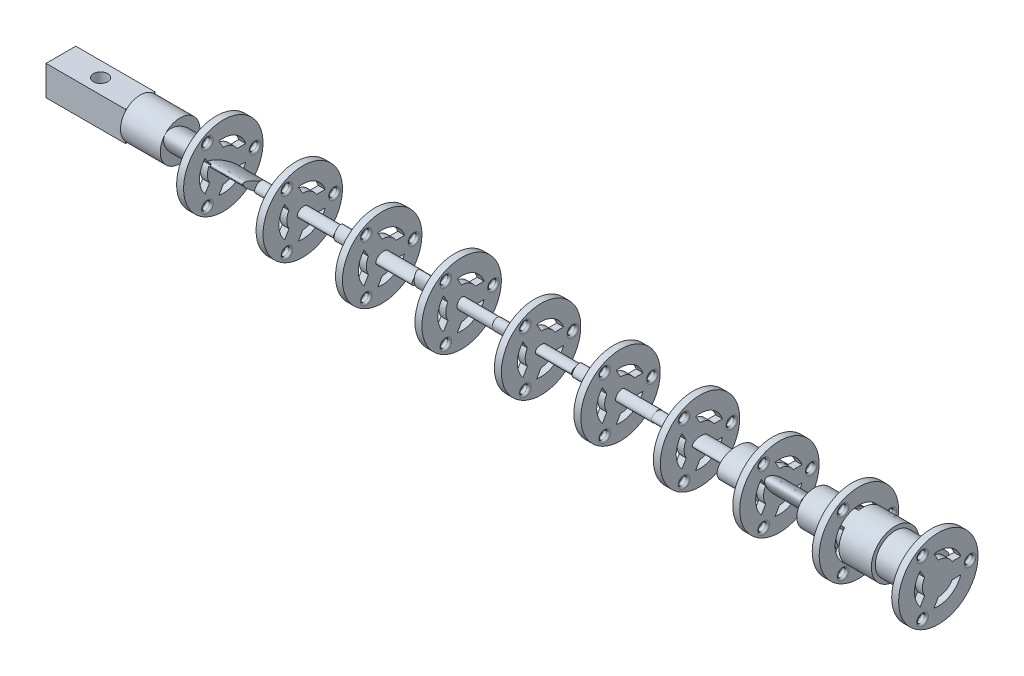
SolidWorks part; units mm, degrees
ref_plane "Front Plane" through (0, 0, 0) normal (0, 0, 1) x (1, 0, 0)
ref_plane "Top Plane" through (0, 0, 0) normal (0, 1, 0) x (1, 0, 0)
ref_plane "Right Plane" through (0, 0, 0) normal (1, 0, 0) x (0, 0, -1)
sketch "Sketch28" plane through (0, 0, 0) normal (1, 0, 0) x (0, 0, -1)
  line L0 (0, 0) -> (0, 30) construction
  line L1 (0, 0) -> (-30, 0) construction
  line L2 (19.0774, 0) -> (-19.0774, 0) construction
  dimension "D1" = 30
sketch "Sketch1" plane through (0, 0, 0) normal (1, 0, 0) x (0, 0, -1)
  line L0 (-3.4986, 3.5721) -> (0, 0) construction
  line L1 (0, 0) -> (-3.565, -3.4916) construction
  line L2 (0, 0) -> (0, 30) construction
  ellipse E0 centre (0, 0) end of major axis (-3.4986, 3.5721) minor radius 4.99
  dimension "ry_1" = 5
  dimension "rz_1" = 4.99
  dimension "phi_1" = 44.404
extrude "Boss-Extrude1" add sketch "Sketch1" along normal blind 10
ref_plane "Plane1" through (10, 0, 0) normal (1, 0, 0) x (0, 0, -1)
sketch "Sketch2" plane through (10, 0, 0) normal (1, 0, 0) x (0, 0, -1)
  line L0 (0, 0) -> (-3.7686, 3.2708) construction
  line L1 (0, 0) -> (-1.737, -2.0014) construction
  line L3 (0, 0) -> (0, 30) construction
  ellipse E0 centre (0, 0) end of major axis (3.7686, -3.2708) minor radius 2.65
  dimension "phi_2" = 49.045
  dimension "ry_2" = 4.99
  dimension "rz_2" = 2.65
extrude "Boss-Extrude2" add sketch "Sketch2" along normal blind 10
ref_plane "Plane2" through (20, 0, 0) normal (1, 0, 0) x (0, 0, -1)
sketch "Sketch3" plane through (20, 0, 0) normal (1, 0, 0) x (0, 0, -1)
  line L0 (0, 0) -> (-4.1746, 2.7518) construction
  line L1 (0, 0) -> (-0.5504, -0.8349) construction
  line L2 (0, 0) -> (0, 30) construction
  ellipse E0 centre (0, 0) end of major axis (-4.1746, 2.7518) minor radius 1
  dimension "ry_3" = 5
  dimension "rz_3" = 1
  dimension "phi_3" = 56.608
extrude "Boss-Extrude3" add sketch "Sketch3" along normal blind 10
ref_plane "Plane3" through (30, 0, 0) normal (1, 0, 0) x (0, 0, -1)
sketch "Sketch4" plane through (30, 0, 0) normal (1, 0, 0) x (0, 0, -1)
  line L0 (-0.6296, 0.7769) -> (0, 0) construction
  line L1 (0, 0) -> (-1.0877, -0.8814) construction
  line L2 (0, 0) -> (0, 30) construction
  ellipse E0 centre (0, 0) end of major axis (-1.0877, -0.8814) minor radius 1
  dimension "ry_4" = 1
  dimension "rz_4" = 1.4
  dimension "phi_4" = 39.018
extrude "Boss-Extrude4" add sketch "Sketch4" along normal blind 10
ref_plane "Plane4" through (40, 0, 0) normal (1, 0, 0) x (0, 0, -1)
sketch "Sketch5" plane through (40, 0, 0) normal (1, 0, 0) x (0, 0, -1)
  line L0 (-0.3391, 0.9407) -> (0, 0) construction
  line L1 (0, 0) -> (-1.3453, -0.485) construction
  line L2 (0, 0) -> (0, 30) construction
  ellipse E0 centre (0, 0) end of major axis (-1.3453, -0.485) minor radius 1
  dimension "ry_5" = 1
  dimension "rz_5" = 1.43
  dimension "phi_5" = 19.824
extrude "Boss-Extrude5" add sketch "Sketch5" along normal blind 10
ref_plane "Plane5" through (50, 0, 0) normal (1, 0, 0) x (0, 0, -1)
sketch "Sketch6" plane through (50, 0, 0) normal (1, 0, 0) x (0, 0, -1)
  line L0 (-0.9649, 0.5281) -> (0, 0) construction
  line L1 (0, 0) -> (-0.8066, -1.4737) construction
  line L2 (0, 0) -> (0, 30) construction
  ellipse E0 centre (0, 0) end of major axis (0.8066, 1.4737) minor radius 1.1
  dimension "ry_6" = 1.1
  dimension "rz_6" = 1.68
  dimension "phi_6" = 61.306
extrude "Boss-Extrude6" add sketch "Sketch6" along normal blind 10
ref_plane "Plane6" through (60, 0, 0) normal (1, 0, 0) x (0, 0, -1)
sketch "Sketch7" plane through (60, 0, 0) normal (1, 0, 0) x (0, 0, -1)
  line L0 (-0.3768, 1.0228) -> (0, 0) construction
  line L1 (0, 0) -> (-1.5764, -0.5808) construction
  line L2 (0, 0) -> (0, 30) construction
  ellipse E0 centre (0, 0) end of major axis (-1.5764, -0.5808) minor radius 1.09
  dimension "ry_7" = 1.09
  dimension "rz_7" = 1.68
  dimension "phi_7" = 20.225
extrude "Boss-Extrude7" add sketch "Sketch7" along normal blind 10
ref_plane "Plane7" through (70, 0, 0) normal (1, 0, 0) x (0, 0, -1)
sketch "Sketch8" plane through (70, 0, 0) normal (1, 0, 0) x (0, 0, -1)
  line L0 (-0.0903, 1.9779) -> (0, 0) construction
  line L1 (0, 0) -> (-1.0689, -0.0488) construction
  line L2 (0, 0) -> (0, 30) construction
  ellipse E0 centre (0, 0) end of major axis (0.0903, -1.9779) minor radius 1.07
  dimension "ry_8" = 1.98
  dimension "rz_8" = 1.07
  dimension "phi_8" = 2.613
extrude "Boss-Extrude8" add sketch "Sketch8" along normal blind 10
ref_plane "Plane8" through (80, 0, 0) normal (1, 0, 0) x (0, 0, -1)
sketch "Sketch9" plane through (80, 0, 0) normal (1, 0, 0) x (0, 0, -1)
  line L0 (-1.0857, 0.3131) -> (0, 0) construction
  line L1 (0, 0) -> (-0.3769, -1.3067) construction
  line L2 (0, 0) -> (0, 30) construction
  ellipse E0 centre (0, 0) end of major axis (-0.3769, -1.3067) minor radius 1.13
  dimension "ry_9" = 1.13
  dimension "rz_9" = 1.36
  dimension "phi_9" = 73.912
extrude "Boss-Extrude9" add sketch "Sketch9" along normal blind 10
ref_plane "Plane9" through (90, 0, 0) normal (1, 0, 0) x (0, 0, -1)
sketch "Sketch10" plane through (90, 0, 0) normal (1, 0, 0) x (0, 0, -1)
  line L0 (-0.6242, 1.5057) -> (0, 0) construction
  line L1 (0, 0) -> (-1.2101, -0.5017) construction
  line L2 (0, 0) -> (0, 30) construction
  ellipse E0 centre (0, 0) end of major axis (-0.6242, 1.5057) minor radius 1.31
  dimension "ry_10" = 1.63
  dimension "rz_10" = 1.31
  dimension "phi_10" = 22.517
extrude "Boss-Extrude10" add sketch "Sketch10" along normal blind 10
ref_plane "Plane10" through (100, 0, 0) normal (1, 0, 0) x (0, 0, -1)
sketch "Sketch11" plane through (100, 0, 0) normal (1, 0, 0) x (0, 0, -1)
  line L0 (-1.4393, 0.0443) -> (0, 0) construction
  line L1 (0, 0) -> (-0.0308, -0.9995) construction
  line L2 (0, 0) -> (0, 30) construction
  ellipse E0 centre (0, 0) end of major axis (-1.4393, 0.0443) minor radius 1
  dimension "ry_11" = 1.44
  dimension "rz_11" = 1
  dimension "phi_11" = 88.236
extrude "Boss-Extrude11" add sketch "Sketch11" along normal blind 10
ref_plane "Plane11" through (110, 0, 0) normal (1, 0, 0) x (0, 0, -1)
sketch "Sketch12" plane through (110, 0, 0) normal (1, 0, 0) x (0, 0, -1)
  line L0 (-0.6772, 0.7358) -> (0, 0) construction
  line L1 (0, 0) -> (-1.111, -1.0226) construction
  line L2 (0, 0) -> (0, 30) construction
  ellipse E0 centre (0, 0) end of major axis (-1.111, -1.0226) minor radius 1
  dimension "ry_12" = 1
  dimension "rz_12" = 1.51
  dimension "phi_12" = 42.628
extrude "Boss-Extrude12" add sketch "Sketch12" along normal blind 10
ref_plane "Plane12" through (120, 0, 0) normal (1, 0, 0) x (0, 0, -1)
sketch "Sketch13" plane through (120, 0, 0) normal (1, 0, 0) x (0, 0, -1)
  line L0 (-0.6241, 0.7813) -> (0, 0) construction
  line L1 (0, 0) -> (-1.0861, -0.8675) construction
  line L2 (0, 0) -> (0, 30) construction
  ellipse E0 centre (0, 0) end of major axis (-1.0861, -0.8675) minor radius 1
  dimension "ry_13" = 1
  dimension "rz_13" = 1.39
  dimension "phi_13" = 38.617
extrude "Boss-Extrude13" add sketch "Sketch13" along normal blind 10
ref_plane "Plane13" through (130, 0, 0) normal (1, 0, 0) x (0, 0, -1)
sketch "Sketch14" plane through (130, 0, 0) normal (1, 0, 0) x (0, 0, -1)
  line L0 (-0.3079, 0.9514) -> (0, 0) construction
  line L1 (0, 0) -> (-1.332, -0.4311) construction
  line L2 (0, 0) -> (0, 30) construction
  ellipse E0 centre (0, 0) end of major axis (1.332, 0.4311) minor radius 1
  dimension "ry_14" = 1
  dimension "rz_14" = 1.4
  dimension "phi_14" = 17.934
extrude "Boss-Extrude14" add sketch "Sketch14" along normal blind 10
ref_plane "Plane14" through (140, 0, 0) normal (1, 0, 0) x (0, 0, -1)
sketch "Sketch15" plane through (140, 0, 0) normal (1, 0, 0) x (0, 0, -1)
  line L0 (-0.095, 0.9955) -> (0, 0) construction
  line L1 (0, 0) -> (-1.9611, -0.1871) construction
  line L2 (0, 0) -> (0, 30) construction
  ellipse E0 centre (0, 0) end of major axis (-1.9611, -0.1871) minor radius 1
  dimension "ry_15" = 1
  dimension "rz_15" = 1.97
  dimension "phi_15" = 5.449
extrude "Boss-Extrude15" add sketch "Sketch15" along normal blind 10
ref_plane "Plane15" through (150, 0, 0) normal (1, 0, 0) x (0, 0, -1)
sketch "Sketch16" plane through (150, 0, 0) normal (1, 0, 0) x (0, 0, -1)
  line L0 (-0.151, 3.3766) -> (0, 0) construction
  line L1 (0, 0) -> (-4.8252, -0.2158) construction
  line L3 (0, 0) -> (0, 30) construction
  ellipse E0 centre (0, 0) end of major axis (-4.8252, -0.2158) minor radius 3.38
  dimension "ry_16" = 3.38
  dimension "rz_16" = 4.83
  dimension "phi_16" = 2.561
extrude "Boss-Extrude16" add sketch "Sketch16" along normal blind 10
ref_plane "Plane16" through (160, 0, 0) normal (1, 0, 0) x (0, 0, -1)
sketch "Sketch17" plane through (160, 0, 0) normal (1, 0, 0) x (0, 0, -1)
  line L0 (-3.5412, 3.5299) -> (0, 0) construction
  line L1 (0, 0) -> (-1.1507, -1.1544) construction
  line L2 (0, 0) -> (0, 30) construction
  ellipse E0 centre (0, 0) end of major axis (-3.5412, 3.5299) minor radius 1.63
  dimension "ry_17" = 5
  dimension "rz_17" = 1.63
  dimension "phi_17" = 45.092
extrude "Boss-Extrude17" add sketch "Sketch17" along normal blind 10
ref_plane "Plane17" through (170, 0, 0) normal (1, 0, 0) x (0, 0, -1)
sketch "Sketch18" plane through (170, 0, 0) normal (1, 0, 0) x (0, 0, -1)
  line L0 (-4.3864, 2.0693) -> (0, 0) construction
  line L1 (0, 0) -> (-1.8816, -3.9885) construction
  line L2 (0, 0) -> (0, 30) construction
  ellipse E0 centre (0, 0) end of major axis (-4.3864, 2.0693) minor radius 4.41
  dimension "ry_18" = 4.85
  dimension "rz_18" = 4.41
  dimension "phi_18" = 64.744
extrude "Boss-Extrude18" add sketch "Sketch18" along normal blind 10
ref_plane "Plane18" through (180, 0, 0) normal (1, 0, 0) x (0, 0, -1)
sketch "Sketch19" plane through (180, 0, 0) normal (1, 0, 0) x (0, 0, -1)
  line L0 (-3.7914, 4.6503) -> (0, 0) construction
  line L1 (0, 0) -> (-4.6503, -3.7914) construction
  line L2 (0, 0) -> (0, 30) construction
  ellipse E0 centre (0, 0) end of major axis (-4.6503, -3.7914) minor radius 6
  dimension "ry_19" = 6
  dimension "rz_19" = 6
  dimension "phi_19" = 39.19
extrude "Boss-Extrude19" add sketch "Sketch19" along normal blind 10
ref_plane "Plane19" through (190, 0, 0) normal (1, 0, 0) x (0, 0, -1)
sketch "Sketch20" plane through (190, 0, 0) normal (1, 0, 0) x (0, 0, -1)
  line L0 (-4.6038, 1.9508) -> (0, 0) construction
  line L1 (0, 0) -> (-1.9508, -4.6038) construction
  line L2 (0, 0) -> (0, 30) construction
  ellipse E0 centre (0, 0) end of major axis (-4.6038, 1.9508) minor radius 5
  dimension "ry_20" = 5
  dimension "rz_20" = 5
  dimension "phi_20" = 67.036
extrude "Boss-Extrude20" add sketch "Sketch20" along normal blind 10
sketch "Sketch21" plane through (0, 0, 0) normal (0, 1, 0) x (1, 0, 0)
  line L0 (0, 0) -> (200, 0) construction
  line L1 (19.125, 0) -> (20.875, 0)
  line L2 (19.125, 0) -> (19.125, -10)
  line L3 (19.125, -10) -> (20.875, -10)
  line L4 (20.875, 0) -> (20.875, -10)
  line L5 (200, -5) -> (200, 5) construction
  point P6 (20, -10)
  dimension "D1" = 20
  dimension "D2" = 10
  dimension "D3" = 1.75
revolve "Revolve1" add sketch "Sketch21" angle 360 about L0
sketch "Sketch22" plane through (20.875, 0, 0) normal (1, 0, 0) x (0, 0, -1)
  line L0 (0, 0) -> (-4, 6.9282) construction
  line L1 (0, 0) -> (-4, -6.9282) construction
  line L2 (0, 0) -> (8, 0) construction
  line L3 (22, 0) -> (-22, 0) construction
  line L4 (-4.5605, 3.899) -> (-3.4641, 2)
  line L5 (-3.4641, -2) -> (-4.5605, -3.899)
  line L6 (5.6569, 2) -> (3.4641, 2)
  line L7 (0, 4) -> (-1.0964, 5.899)
  line L8 (-1.0964, -5.899) -> (0, -4)
  line L9 (3.4641, -2) -> (5.6569, -2)
  circle A0 centre (-4, 6.9282) radius 1
  circle A1 centre (-4, -6.9282) radius 1
  circle A2 centre (8, 0) radius 1
  arc A3 (-3.4641, 2) -> (-3.4641, -2) centre (0, 0) ccw
  arc A5 (-4.5605, -3.899) -> (-4.5605, 3.899) centre (0, 0) cw
  arc A7 (-1.0964, 5.899) -> (5.6569, 2) centre (0, 0) cw
  arc A8 (3.4641, 2) -> (0, 4) centre (0, 0) ccw
  arc A9 (5.6569, -2) -> (-1.0964, -5.899) centre (0, 0) cw
  arc A10 (0, -4) -> (3.4641, -2) centre (0, 0) ccw
  point P30 (0, 0)
  dimension "D4" = 2
  dimension "D7" = 6
  dimension "D9" = 4
  dimension "D1" = 120
  dimension "D2" = 120
  dimension "D3" = 8
  dimension "D5" = 2
  dimension "D6" = 2
  dimension "D8" = 3
extrude "Cut-Extrude1" cut sketch "Sketch22" against normal up to surface (1.75 mm away) from offset 1 up to face at (19.125, -3.2708, -3.7686)
fillet "Fillet2" radius 0.5 6 edges at (20.875, -6.9282, 3) (19.125, -6.9282, 5) (20.875, 6.9282, 3) (19.125, 6.9282, 5) (20.875, 0, -9) (19.125, 0, -7)
pattern_linear "LPattern1" count 10 spacing 20 along (1, 0, 0) of "Revolve1", "Cut-Extrude1", "Fillet2"
sketch "Sketch23" plane through (0, 0, 0) normal (-1, 0, 0) x (0, 0, 1)
  line L1 (-3.75, 3.75) -> (3.75, 3.75)
  line L2 (-3.75, 3.75) -> (-3.75, -3.75)
  line L3 (-3.75, -3.75) -> (3.75, -3.75)
  line L4 (3.75, 3.75) -> (3.75, -3.75)
  line L5 (-3.75, 3.75) -> (3.75, -3.75) construction
  line L6 (-3.75, -3.75) -> (3.75, 3.75) construction
  point P0 (0, 0)
  dimension "D1" = 7.5
extrude "Boss-Extrude21" add sketch "Sketch23" along normal blind 20
sketch "Sketch26" plane through (0, -3.75, 0) normal (0, -1, 0) x (-1, 0, 0)
  line L0 (20, 3.75) -> (0, 3.75) construction
  point P0 (10, 0)
  point P7 (10, 3.75)
hole_wizard "M3 Clearance Hole1" positions "Sketch26" profile "Sketch27" hole size "M3" standard "ANSI Metric" end condition up to next
sketch "Sketch27" plane through (-10, -3.75, 0) normal (1, 0, 0) x (0, 0, -1)
  line L0 (0, 0) -> (0, 7.5)
  line L1 (0, 7.5) -> (1.8, 7.5)
  line L2 (1.8, 7.5) -> (1.8, 0)
  line L5 (1.8, 0) -> (0, 0)
  line L11 (0, -6.35) -> (0, 107.95) construction
  dimension "Thru Hole Dia." = 3.6
  dimension "Thru Hole Depth" = 7.5
